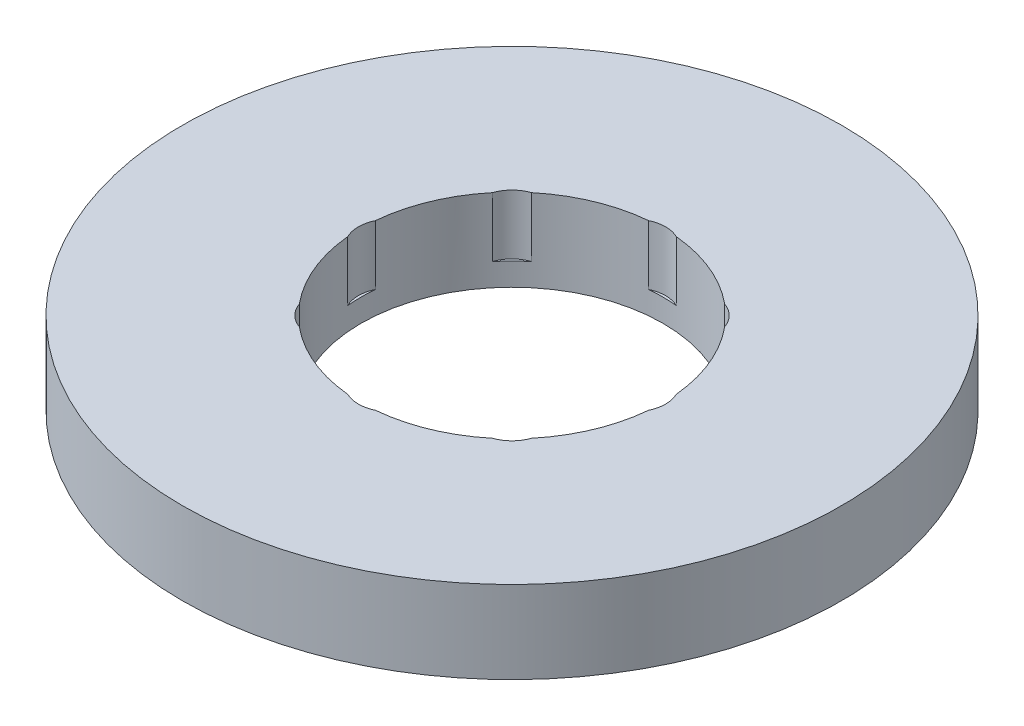
SolidWorks part; units mm, degrees
ref_plane "Front Plane" through (0, 0, 0) normal (0, 0, 1) x (1, 0, 0)
ref_plane "Top Plane" through (0, 0, 0) normal (0, 1, 0) x (1, 0, 0)
ref_plane "Right Plane" through (0, 0, 0) normal (1, 0, 0) x (0, 0, -1)
sketch "Sketch1" plane through (0, 0, 0) normal (0, 1, 0) x (1, 0, 0)
  circle A0 centre (0, 0) radius 60
  dimension "FLANGE_OD" = 120
extrude "Boss-Extrude1" add sketch "Sketch1" along normal blind 15
sketch "Sketch2" plane through (0, 0, 0) normal (0, 1, 0) x (1, 0, 0)
  circle A0 centre (0, 0) radius 27.5
  dimension "BORE_D" = 55
extrude "Cut-Extrude1" cut sketch "Sketch2" along normal through all
sketch "Sketch3" plane through (0, 15, 0) normal (0, 1, 0) x (1, 0, 0)
  circle A0 centre (0, 0) radius 22.1873 construction
  circle A1 centre (-22.1873, 0) radius 5.7772
  dimension "BOLT_D" = 11.5545
  dimension "BOLT_PCD" = 44.3747
extrude "Cut-Extrude2" cut sketch "Sketch3" against normal blind 10.8632
pattern_circular "CirPattern1" count 8 over 360 about axis through (0, 0, 0) along (0, 1, 0) of "Cut-Extrude2"
